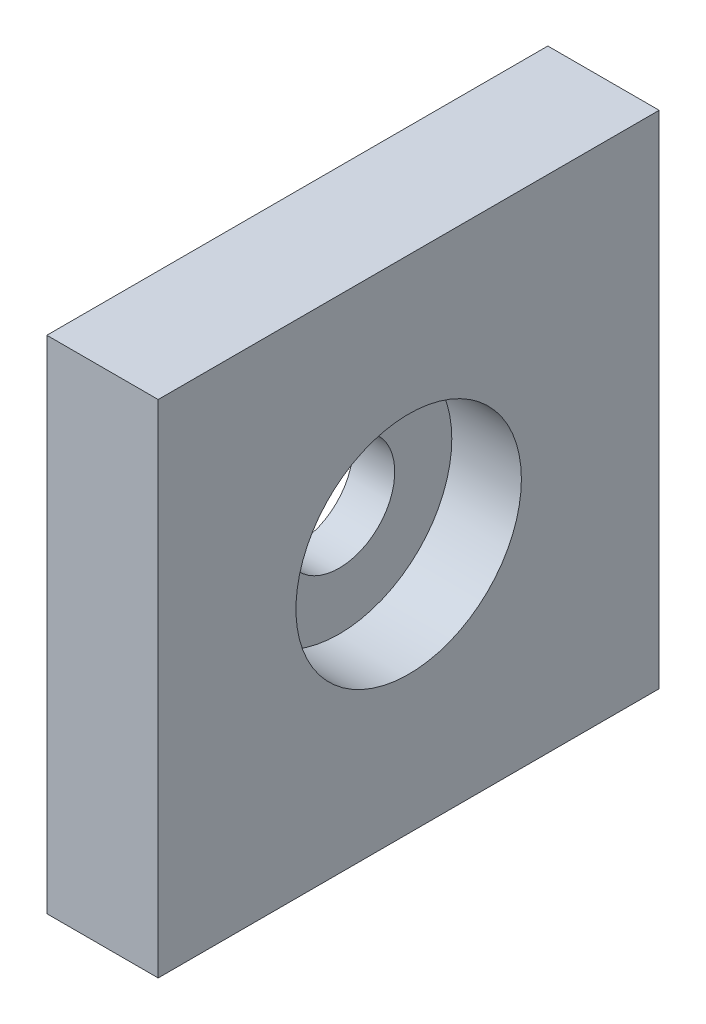
SolidWorks part; units mm, degrees
ref_plane "Plan de face" through (0, 0, 0) normal (0, 0, 1) x (1, 0, 0)
ref_plane "Plan de dessus" through (0, 0, 0) normal (0, 1, 0) x (1, 0, 0)
ref_plane "Plan de droite" through (0, 0, 0) normal (1, 0, 0) x (0, 0, -1)
sketch "Esquisse1" plane through (0, 0, 0) normal (0, 1, 0) x (1, 0, 0)
  line L24 (0, 0) -> (0, 36)
  line L25 (0, 36) -> (8, 36)
  line L26 (8, 36) -> (8, 0)
  line L27 (8, 0) -> (0, 0)
extrude "Boss.-Extru.3" add sketch "Esquisse1" along normal blind 36 contours L27 L26 L25 L24 region at (4, 0, -18)
sketch "Esquisse9" plane through (8, 0, 0) normal (1, 0, 0) x (0, 0, -1)
  line L0 (18, 0) -> (0, 0) construction
  line L2 (18, 0) -> (18, 18) construction
  circle A0 centre (18, 18) radius 8.1
extrude "Enlèv. mat.-Extru.1" cut sketch "Esquisse9" against normal blind 10
sketch "Esquisse10" plane through (0, 0, 0) normal (-1, 0, 0) x (0, 0, 1)
  circle A0 centre (-18, 18) radius 8.1
  circle A1 centre (-18, 18) radius 4
extrude "Boss.-Extru.4" add sketch "Esquisse10" against normal blind 3
sketch "Esquisse13" plane through (0, 0, 0) normal (0, -1, 0) x (1, 0, 0)
  line L0 (0, 0) -> (8, 0) construction
  line L1 (8, 0) -> (8, -8) construction
  line L2 (8, -36) -> (8, 0) construction
  line L3 (8, -8) -> (0, -8) construction
  line L4 (0, 0) -> (0, -36) construction
  line L5 (0, -8) -> (0, 0) construction
  line L6 (0, 0) -> (8, -8) construction
  line L7 (8, -8) -> (8, 0) construction
  line L8 (8, 0) -> (0, -8) construction
  line L9 (0, -36) -> (8, -36) construction
  line L10 (8, -36) -> (8, -28) construction
  line L11 (8, -28) -> (0, -28) construction
  line L12 (0, -28) -> (0, -36) construction
  line L13 (0, -36) -> (8, -28) construction
  line L14 (8, -28) -> (0, -28) construction
  line L15 (0, -28) -> (8, -36) construction
  circle A0 centre (4, -4) radius 2
  circle A1 centre (4, -32) radius 2
  dimension "D1" = 4
  dimension "D5" = 4
  dimension "D2" = 8
  dimension "D3" = 8
  dimension "D4" = 8
  dimension "D6" = 8
extrude "Enlèv. mat.-Extru.2" cut sketch "Esquisse13" against normal blind 15
sketch "Esquisse14" plane through (8, 0, 0) normal (1, 0, 0) x (0, 0, -1)
  line L0 (0, 0) -> (36, 0) construction
  line L1 (36, 0) -> (36, 36) construction
  circle A0 centre (18, 18) radius 6
  circle A1 centre (18, 18) radius 8.1
  dimension "D1" = 16.2
  dimension "D2" = 12
  dimension "D3" = 36
  dimension "D4" = 36
sketch "Esquisse15" plane through (0, 0, 0) normal (-1, 0, 0) x (0, 0, 1)
  line L0 (-36, 36) -> (-36, 0)
  line L1 (-36, 0) -> (0, 0)
  circle A0 centre (-18, 18) radius 6
  dimension "D3" = 12
  dimension "D1" = 36
  dimension "D2" = 36
sketch "Esquisse16" plane through (0, 0, -36) normal (0, 0, -1) x (-1, 0, 0)
  line L0 (-8, 36) -> (0, 36)
  line L1 (0, 36) -> (-8, 36) construction
  line L2 (-8, 36) -> (-8, 0)
  dimension "D1" = 8
  dimension "D2" = 36
